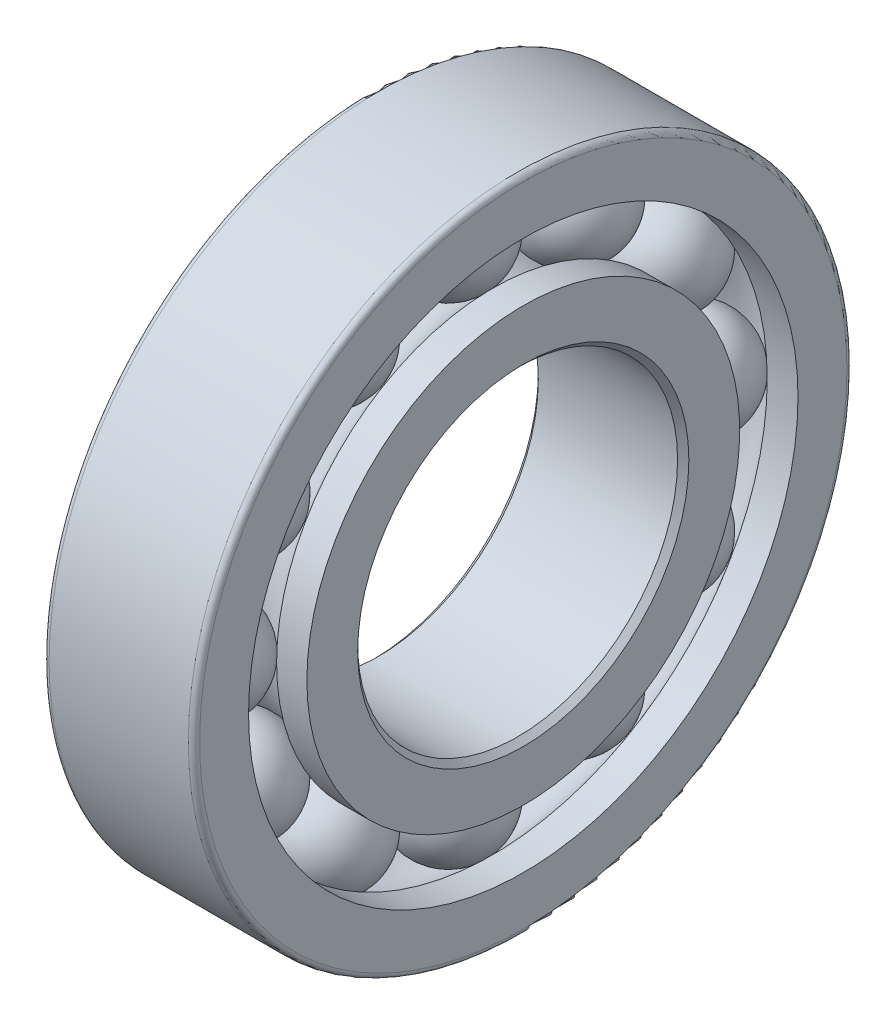
SolidWorks part; units mm, degrees
ref_plane "Front Plane" through (0, 0, 0) normal (0, 0, 1) x (1, 0, 0)
ref_plane "Top Plane" through (0, 0, 0) normal (0, 1, 0) x (1, 0, 0)
ref_plane "Right Plane" through (0, 0, 0) normal (1, 0, 0) x (0, 0, -1)
sketch "Sketch1" plane through (0, 0, 0) normal (0, 1, 0) x (1, 0, 0)
  line L0 (-25.3067, 0) -> (0, 0) construction
  line L1 (0, 0) -> (0, 16.05) construction
  line L3 (4, 17.5) -> (-4, 17.5)
  line L4 (4, 17.5) -> (4, 14.6)
  line L5 (4, 14.6) -> (-4, 14.6)
  line L6 (-4, 17.5) -> (-4, 14.6)
  line L7 (4, 17.5) -> (-4, 14.6) construction
  line L8 (4, 14.6) -> (-4, 17.5) construction
  line L9 (4, 11.5) -> (-4, 11.5)
  line L10 (4, 11.5) -> (4, 8.5)
  line L11 (4, 8.5) -> (-4, 8.5)
  line L12 (-4, 11.5) -> (-4, 8.5)
  line L13 (4, 11.5) -> (-4, 8.5) construction
  line L14 (4, 8.5) -> (-4, 11.5) construction
  circle A0 centre (0, 13.0311) radius 2.8381
  point P8 (0, 10)
  dimension "D1" = 8.5
  dimension "D2" = 11.5
  dimension "D3" = 14.6
  dimension "D4" = 17.5
  dimension "D5" = 8
revolve "Revolve1" add sketch "Sketch1" angle 360 about L0 region at (0, 0, -16.2573) region at (0, 0, -9.7831)
ref_axis "Axis1" through (4, 0, 0) along (-1, 0, 0)
sketch "Sketch2" plane through (0, 0, 0) normal (0, 0, 1) x (1, 0, 0)
  line L0 (2.8, 13.03) -> (-2.8, 13.03)
  circle A0 centre (0, 13.03) radius 2.8
  dimension "D1" = 5.6
  dimension "D2" = 13.03
revolve "Revolve2" add sketch "Sketch2" angle 360 about L0 region at (0, 14.2184, 0)
pattern_circular "CirPattern3" count 12 over 360 about axis through (4, 0, 0) along (-1, 0, 0) of bodies 103
fillet "Fillet1" radius 0.3 2 edges at (4, 0, 17.5) (-4, 0, 17.5)
chamfer "Chamfer1" distance 0.3 angle 45 2 edges at (4, 0, 8.5) (-4, 0, 8.5)
